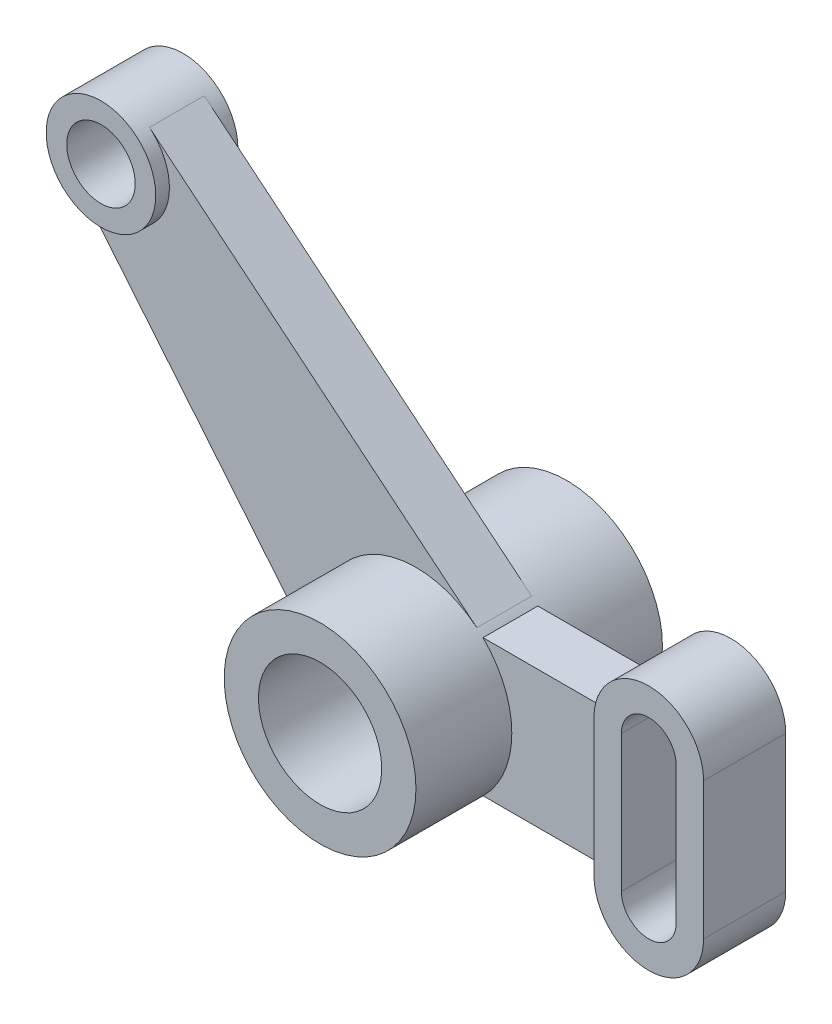
SolidWorks part; units mm, degrees
ref_plane "Plano frontal" through (0, 0, 0) normal (0, 0, 1) x (1, 0, 0)
ref_plane "Plano superior" through (0, 0, 0) normal (0, 1, 0) x (1, 0, 0)
ref_plane "Plano direito" through (0, 0, 0) normal (1, 0, 0) x (0, 0, -1)
sketch "Esboço2" plane through (0, 0, 0) normal (0, 0, 1) x (1, 0, 0)
  line L0 (90, -25) -> (90, 25) construction
  line L9 (0, 0) -> (-110, 110) construction
  line L10 (0, 0) -> (-150, 0) construction
  line L11 (80, -25) -> (80, 25)
  line L12 (100, -25) -> (100, 25)
  line L13 (70, -25) -> (70, 25)
  line L14 (110, -25) -> (110, 25)
  line L15 (24.4949, 25) -> (70, 25)
  line L16 (70, -25) -> (24.4949, -25)
  line L17 (-97.2874, 125.4399) -> (22.2471, 27.0198)
  line L18 (-125.4399, 97.2874) -> (-27.0198, -22.2471)
  arc A1 (80, -25) -> (100, -25) centre (90, -25) ccw
  arc A3 (100, 25) -> (80, 25) centre (90, 25) ccw
  circle A4 centre (0, 0) radius 22.5
  circle A5 centre (-110, 110) radius 12.5
  circle A6 centre (-110, 110) radius 20
  circle A7 centre (0, 0) radius 35
  arc A8 (110, 25) -> (70, 25) centre (90, 25) ccw
  arc A9 (70, -25) -> (110, -25) centre (90, -25) ccw
  point P2 (90, 0)
  point P16 (0, 0)
  point P18 (0, 0)
  point P24 (0, 0)
  point P25 (0, 0)
  dimension "D3" = 10
  dimension "D5" = 45
  dimension "D9" = 25
  dimension "D10" = 70
  dimension "D11" = 40
  dimension "D8" = 90
  dimension "D4" = 20
  dimension "D2" = 50
  dimension "D6" = 110
  dimension "D7" = 45
  dimension "D12" = 110
extrude "Ressalto-extrusão1" add sketch "Esboço2" along normal mid plane 90 contours A7 A4 region at (-1.8149, -33.9616, 0)
extrude "Ressalto-extrusão2" add sketch "Esboço2<3>" along normal mid plane 30 separate body contours A6 A5 | A8 region at (70.9849, 0, 0) region at (-123.7421, 123.7421, 0)
sketch "Esboço2<3>" plane through (0, 0, 0) normal (0, 0, 1) x (1, 0, 0) same geometry as "Esboço2"
extrude "Ressalto-extrusão4" add sketch "Esboço2<5>" along normal mid plane 20 contours A7 A6 | A7 region at (50.7489, 0, 0) region at (-56.966, 56.966, 0)
sketch "Esboço2<5>" plane through (0, 0, 0) normal (0, 0, 1) x (1, 0, 0) same geometry as "Esboço2"
